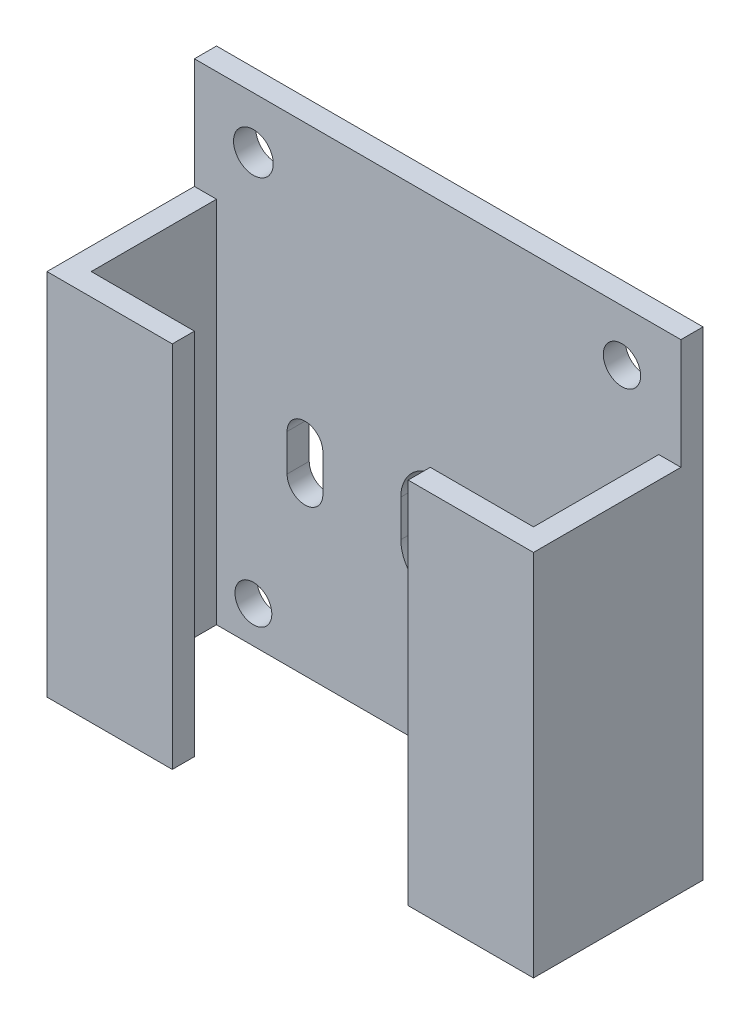
SolidWorks part; units mm, degrees
ref_plane "Front Plane" through (0, 0, 0) normal (0, 0, 1) x (1, 0, 0)
ref_plane "Top Plane" through (0, 0, 0) normal (0, 1, 0) x (1, 0, 0)
ref_plane "Right Plane" through (0, 0, 0) normal (1, 0, 0) x (0, 0, -1)
sketch "Sketch1" plane through (0, 0, 0) normal (1, 0, 0) x (0, 0, -1)
  line L0 (0, 0) -> (0, -65)
  line L1 (0, -65) -> (-23, -65)
  line L2 (-23, -65) -> (-23, 0)
  line L3 (-23, 0) -> (0, 0)
  dimension "D1" = 65
  dimension "D2" = 23
extrude "Boss-Extrude1" add sketch "Sketch1" against normal blind 66
sketch "Sketch2" plane through (0, 0, 0) normal (0, 1, 0) x (1, 0, 0)
  line L0 (-33, 0) -> (-33, -23) construction
  line L1 (-66, 0) -> (0, 0) construction
  line L2 (-66, -23) -> (0, -23) construction
  line L3 (-66, -11.5) -> (0, -11.5) construction
  line L4 (-66, 0) -> (-66, -23) construction
  line L5 (0, 0) -> (0, -23) construction
  line L7 (-63, -20) -> (-3, -20)
  line L8 (-63, -20) -> (-63, -3)
  line L9 (-63, -3) -> (-3, -3)
  line L10 (-3, -20) -> (-3, -3)
  line L11 (-63, -20) -> (-3, -3) construction
  line L12 (-63, -3) -> (-3, -20) construction
  point P12 (-33, -11.5)
  point P17 (-3, -11.5)
  point P18 (-63, -11.5)
  dimension "D1" = 3
  dimension "D2" = 3
  dimension "D3" = 3
  dimension "D4" = 3
extrude "Cut-Extrude1" cut sketch "Sketch2" against normal through all
sketch "Sketch3" plane through (0, 0, 23) normal (0, 0, 1) x (1, 0, 0)
  line L0 (-66, 0) -> (0, 0) construction
  line L1 (-49, 0) -> (-17, 0)
  line L2 (-49, 0) -> (-49, -65)
  line L3 (-49, -65) -> (-17, -65)
  line L4 (-17, 0) -> (-17, -65)
  line L5 (-66, 0) -> (-66, -65) construction
  line L6 (0, 0) -> (0, -65) construction
  dimension "D1" = 17
  dimension "D2" = 17
  dimension "D3" = 32
  dimension "D4" = 65
extrude "Cut-Extrude2" cut sketch "Sketch3" against normal up to next
sketch "Sketch5" plane through (0, 0, 0) normal (0, 0, -1) x (-1, 0, 0)
  line L0 (33, -65) -> (33, 0) construction
  line L1 (66, -65) -> (0, -65) construction
  line L2 (66, 0) -> (0, 0) construction
  line L3 (0, -32.5) -> (66, -32.5) construction
  line L4 (0, -65) -> (0, 0) construction
  line L5 (66, -65) -> (66, 0) construction
  line L6 (66, -37.5) -> (0, -37.5) construction
  line L7 (33, -37.5) -> (33, -42.5) construction
  line L8 (38, -37.5) -> (38, -42.5)
  line L9 (28, -37.5) -> (28, -42.5)
  line L10 (15, -37.5) -> (15, -42.5) construction
  line L11 (17.4772, -37.5) -> (17.4772, -42.5)
  line L12 (12.5228, -37.5) -> (12.5228, -42.5)
  line L13 (51, -37.5) -> (51, -42.5) construction
  line L14 (53.4248, -37.5) -> (53.4248, -42.5)
  line L15 (48.5752, -37.5) -> (48.5752, -42.5)
  circle A1 centre (8, -7) radius 2.5306
  circle A2 centre (58, -7) radius 2.6928
  arc A5 (38, -37.5) -> (28, -37.5) centre (33, -37.5) ccw
  arc A6 (28, -42.5) -> (38, -42.5) centre (33, -42.5) ccw
  arc A7 (17.4772, -37.5) -> (12.5228, -37.5) centre (15, -37.5) ccw
  arc A8 (12.5228, -42.5) -> (17.4772, -42.5) centre (15, -42.5) ccw
  arc A9 (53.4248, -37.5) -> (48.5752, -37.5) centre (51, -37.5) ccw
  arc A10 (48.5752, -42.5) -> (53.4248, -42.5) centre (51, -42.5) ccw
  circle A11 centre (8, -60) radius 2.5
  circle A12 centre (58, -60) radius 2.5
  point P22 (15, -40)
  point P24 (33, -40)
  point P34 (51, -40)
  dimension "D2" = 5
  dimension "D7" = 5
  dimension "D8" = 18
  dimension "D12" = 5
  dimension "D13" = 5
  dimension "D1" = 10
  dimension "D3" = 8
  dimension "D4" = 8
  dimension "D5" = 7
  dimension "D6" = 7
  dimension "D9" = 5
  dimension "D10" = 18
  dimension "D11" = 5
  dimension "D14" = 5
  dimension "D15" = 5
  dimension "D16" = 8
  dimension "D17" = 8
extrude "Cut-Extrude3" cut sketch "Sketch5" against normal up to next
sketch "Sketch6" plane through (0, 0, 23) normal (0, 0, 1) x (1, 0, 0)
  line L0 (-49, 0) -> (-49, -65) construction
  line L1 (-66, 0) -> (-49, 0)
  line L2 (-66, 0) -> (-66, -15)
  line L3 (-66, -15) -> (-49, -15)
  line L4 (-49, 0) -> (-49, -15)
  line L5 (0, 0) -> (0, -65) construction
  line L6 (-17, 0) -> (0, 0)
  line L7 (-17, 0) -> (-17, -15)
  line L8 (-17, -15) -> (0, -15)
  line L9 (0, 0) -> (0, -15)
  dimension "D1" = 15
  dimension "D2" = 15
  dimension "D3" = 17
  dimension "D4" = 17
extrude "Cut-Extrude4" cut sketch "Sketch6" against normal up to surface (20 mm away) up to face at (-60.5, -60, 3)
